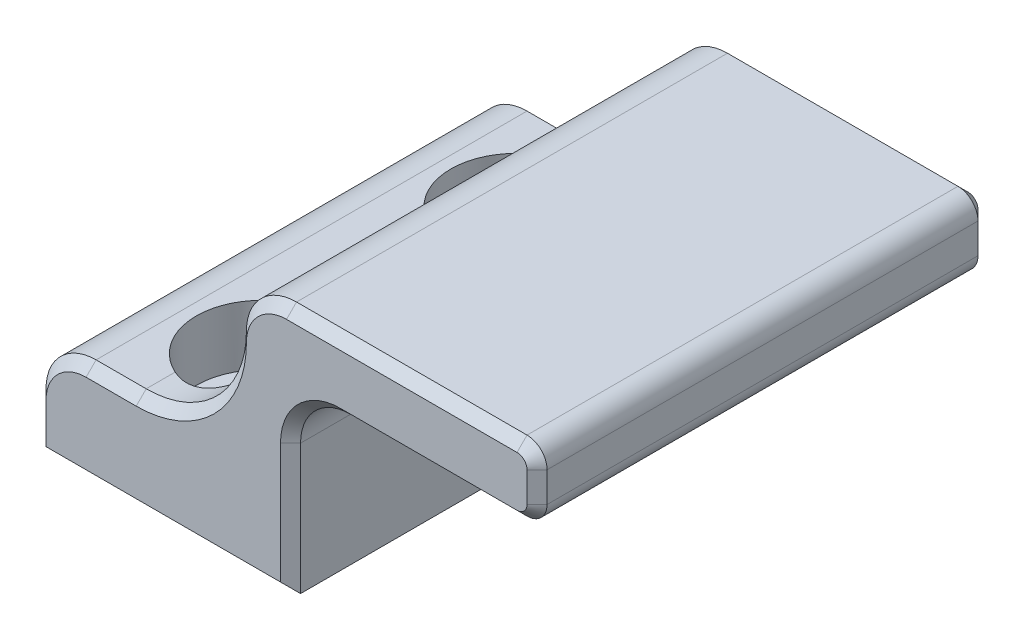
SolidWorks part; units mm, degrees
ref_plane "Front Plane" through (0, 0, 0) normal (0, 0, 1) x (1, 0, 0)
ref_plane "Top Plane" through (0, 0, 0) normal (0, 1, 0) x (1, 0, 0)
ref_plane "Right Plane" through (0, 0, 0) normal (1, 0, 0) x (0, 0, -1)
sketch "Sketch1" plane through (0, 0, 0) normal (0, 0, 1) x (1, 0, 0)
  line L0 (-22.7, -12.5) -> (2.7, -12.5)
  line L5 (2.7, -12.5) -> (2.7, 5.5)
  line L6 (2.7, 5.5) -> (27.3, 5.5)
  line L7 (27.3, 5.5) -> (27.3, 12.5)
  line L8 (27.3, 12.5) -> (-2.7, 12.5)
  line L9 (-2.7, 12.5) -> (-2.7, -2.5)
  line L10 (-2.7, -2.5) -> (-22.7, -2.5)
  line L11 (-22.7, -2.5) -> (-22.7, -12.5)
  line L12 (0, 12.5) -> (0, -12.5) construction
  line L13 (-2.7, 0) -> (2.7, 0) construction
  point P13 (0, 0)
  point P22 (0, 0)
  dimension "D1" = 18
  dimension "D2" = 30
  dimension "D3" = 25.4
  dimension "D4" = 20
  dimension "D5" = 10
  dimension "D6" = 7
extrude "Boss-Extrude1" add sketch "Sketch1" along normal mid plane 45
sketch "Sketch3" plane through (0, -2.5, 0) normal (0, 1, 0) x (1, 0, 0)
  line L2 (-22.7, -22.5) -> (2.7, -22.5) construction
  line L3 (-22.7, -22.5) -> (2.7, -22.5) construction
  circle A0 centre (-10, -12.7) radius 6.5
  circle A1 centre (-10, -12.7) radius 4
  point P0 (-10.8843, -12.7)
  point P3 (-10, -22.5)
  dimension "D1" = 13
  dimension "D2" = 8
  dimension "D3" = 12.7
extrude "Cut-Extrude1" cut sketch "Sketch3" against normal through all contours A1
extrude "Cut-Extrude2" cut sketch "Sketch3<4>" against normal blind 6
sketch "Sketch3<4>" plane through (0, -2.5, 0) normal (0, 1, 0) x (1, 0, 0) same geometry as "Sketch3"
mirror "Mirror1" about plane through (0, 0, 0) normal (0, 0, 1) of "Cut-Extrude2", "Cut-Extrude1"
sketch "Sketch9" plane through (0, 12.5, 0) normal (0, 1, 0) x (1, 0, 0)
  line L0 (10.9078, 11.1) -> (21.2078, -11.1) construction
  line L1 (27.3, -22.5) -> (27.3, 22.5) construction
  circle A0 centre (10.9078, 11.1) radius 1.0922
  circle A1 centre (21.2078, -11.1) radius 1.0922
  point P4 (16.0578, 0)
  dimension "D3" = 2.1844
  dimension "D1" = 22.2
  dimension "D2" = 10.3
  dimension "D4" = 5
extrude "Cut-Extrude3" [suppressed] cut sketch "Sketch9" against normal through all
fillet "Fillet1" radius 10 1 edges at (-2.7, -2.5, 0)
fillet "Fillet2" radius 5 3 edges at (2.7, 5.5, 0) (-22.7, -2.5, 0) (-2.7, 12.5, 0)
fillet "Fillet4" radius 2 2 edges at (27.3, 12.5, 0) (27.3, 5.5, 0)
chamfer "Chamfer1" distance 1 angle 45 26 edges at (27.3, 9, 22.5) (16.5, 5.5, 22.5) (4.1645, 4.0355, 22.5) (2.7, -6, 22.5) (-10, -12.5, 22.5) (-22.7, -10, 22.5) (-15.2, -2.5, 22.5) (-5.6289, 0.4289, 22.5) (13.8, 12.5, 22.5) (-15.2, -2.5, -22.5) (-22.7, -10, -22.5) (-10, -12.5, -22.5) (2.7, -6, -22.5) (4.1645, 4.0355, -22.5) (16.5, 5.5, -22.5) (27.3, 9, -22.5) (13.8, 12.5, -22.5) (-5.6289, 0.4289, -22.5) (26.7142, 6.0858, 22.5) (-21.2355, -3.9645, 22.5) (26.7142, 11.9142, 22.5) (-21.2355, -3.9645, -22.5) (26.7142, 6.0858, -22.5) (26.7142, 11.9142, -22.5) (-1.2355, 11.0355, 22.5) (-1.2355, 11.0355, -22.5)
